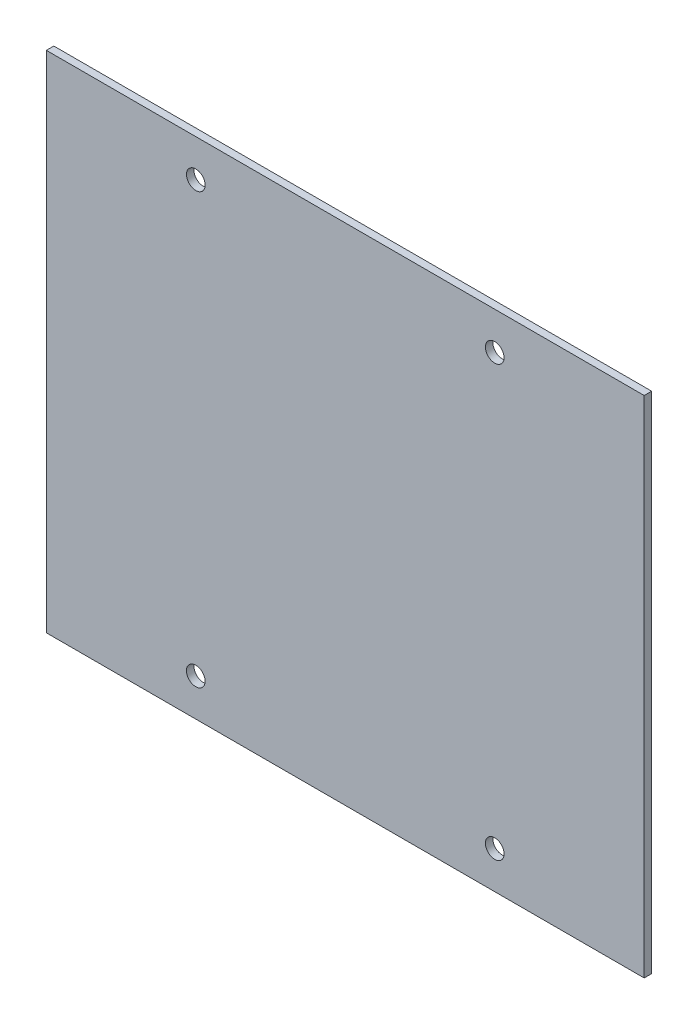
SolidWorks part; units mm, degrees
ref_plane "Ön Düzlem" through (0, 0, 0) normal (0, 0, 1) x (1, 0, 0)
ref_plane "Üst Düzlem" through (0, 0, 0) normal (0, 1, 0) x (1, 0, 0)
ref_plane "Sağ Düzlem" through (0, 0, 0) normal (1, 0, 0) x (0, 0, -1)
sketch "Çizim1" plane through (0, 0, 0) normal (0, 0, 1) x (1, 0, 0)
  line L0 (40, 135) -> (40, 0) construction
  line L1 (0, 0) -> (160, 0)
  line L2 (0, 0) -> (0, 135)
  line L3 (0, 135) -> (160, 135)
  line L4 (160, 0) -> (160, 135)
  line L5 (120, 135) -> (120, 0) construction
  line L6 (0, 125) -> (160, 125) construction
  line L7 (0, 10) -> (160, 10) construction
  circle A0 centre (40, 125) radius 2.5
  circle A1 centre (120, 125) radius 2.5
  circle A2 centre (40, 10) radius 2.5
  circle A3 centre (120, 10) radius 2.5
  dimension "D6" = 10
  dimension "D8" = 5
  dimension "D1" = 40
  dimension "D2" = 40
  dimension "D3" = 10
  dimension "D4" = 10
  dimension "D5" = 135
  dimension "D7" = 160
extrude "Yükseklik-Ekstrüzyon1" add sketch "Çizim1" along normal blind 2
